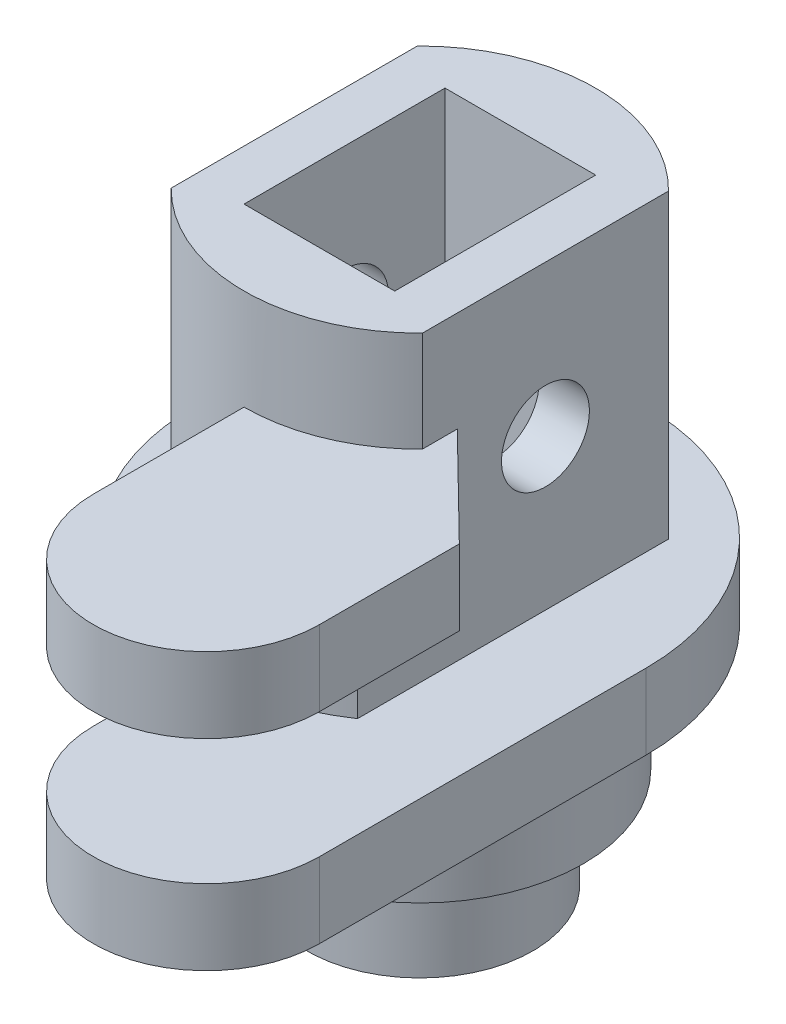
SolidWorks part; units mm, degrees
other "Markup1"
sketch "Sketch25" plane through (9, 15, 17.5) normal (0.6941, 0.3653, 0.6203) x (0.635, -0.7165, -0.2888)
ref_plane "Front Plane" through (0, 0, 0) normal (0, 0, 1) x (1, 0, 0)
ref_plane "Top Plane" through (0, 0, 0) normal (0, 1, 0) x (1, 0, 0)
ref_plane "Right Plane" through (0, 0, 0) normal (1, 0, 0) x (0, 0, -1)
sketch "Sketch1" plane through (0, 0, 0) normal (0, 1, 0) x (1, 0, 0)
  circle A0 centre (0, 0) radius 9
  dimension "D1" = 18
extrude "main body" add sketch "Sketch1" along normal blind 15
sketch "Sketch4" plane through (0, 0, 0) normal (0, -1, 0) x (1, 0, 0)
  circle A0 centre (0, 0) radius 6.5
  circle A1 centre (0, 0) radius 9 construction
  dimension "D1" = 13
extrude "Boss-Extrude3" add sketch "Sketch4" along normal blind 5 contours A0
sketch "Sketch5" plane through (0, -5, 0) normal (0, -1, 0) x (1, 0, 0)
  circle A0 centre (0, 0) radius 4.5
  circle A1 centre (0, 0) radius 6.5 construction
  dimension "D1" = 9
extrude "Boss-Extrude4" add sketch "Sketch5" along normal blind 4 contours A0
ref_plane "Plane1" through (0, 8, 0) normal (0, 1, 0) x (1, 0, 0)
sketch "Sketch9" plane through (0, 0, 0) normal (0, -1, 0) x (1, 0, 0)
  line L0 (0, 9) -> (0, 13)
  line L1 (9, 0) -> (9, 13)
  line L2 (0, 13) -> (9, 13) construction
  circle A0 centre (0, 0) radius 9 construction
  arc A2 (9, 0) -> (0, 9) centre (0, 0) ccw
  arc A3 (9, 13) -> (0, 13) centre (4.5, 13) ccw
  dimension "D2" = 4.5
  dimension "D1" = 4
extrude "arm atttach" add sketch "Sketch9" against normal blind 3
ref_plane "Plane2" through (5, 0, 0) normal (1, 0, 0) x (0, 0, -1)
sketch "Sketch11" plane through (5, 0, 0) normal (1, 0, 0) x (0, 0, -1)
  line L0 (9, 0) -> (9, 15) construction
  line L1 (-9, 15) -> (9, 15)
  line L2 (-9, 15) -> (-9, 3)
  line L3 (-9, 3) -> (9, 3)
  line L4 (9, 15) -> (9, 3)
  dimension "D1" = 12
extrude "Cut-Extrude1" cut sketch "Sketch11" along normal blind 5
sketch "Sketch13" plane through (0, 8, 0) normal (0, 1, 0) x (1, 0, 0)
  line L0 (0, -13) -> (0, -9)
  line L1 (9, -13) -> (9, -7.4292)
  line L2 (9, -7.4292) -> (5, -3.5092)
  line L3 (5, -7.4833) -> (5, 7.4833) construction
  line L4 (5, -3.5092) -> (5, -7.4833)
  arc A0 (0, -13) -> (9, -13) centre (4.5, -13) ccw
  arc A1 (0, -9) -> (5, -7.4833) centre (0, 0) ccw
extrude "arm attach" add sketch "Sketch13" along normal blind 3
ref_plane "Plane4" through (-5, 0, 0) normal (-1, 0, 0) x (0, 0, 1)
sketch "Sketch19" plane through (0, 15, 0) normal (0, 1, 0) x (1, 0, 0)
  line L0 (0, -7) -> (0, -9)
  line L1 (7.0839, -5.5514) -> (5.6441, -4.1405)
  line L2 (9, -7.4292) -> (5, -3.5092) construction
  arc A0 (5.6441, -4.1405) -> (0, -7) centre (0, 0) ccw
  arc A1 (7.0839, -5.5514) -> (0, -9) centre (0, 0) ccw
  dimension "D1" = 14
extrude "Cut-Extrude5" cut sketch "Sketch19" against normal up to surface (12 mm away) up to face at (4.8416, 3, 6.5616)
sketch "Sketch14" plane through (0, 15, 0) normal (0, 1, 0) x (1, 0, 0)
  line L1 (-3, 4) -> (3, 4)
  line L2 (-3, 4) -> (-3, -4)
  line L3 (-3, -4) -> (3, -4)
  line L4 (3, 4) -> (3, -4)
  line L5 (-3, 4) -> (3, -4) construction
  line L6 (-3, -4) -> (3, 4) construction
  point P0 (0, 0)
  dimension "D1" = 6
  dimension "D2" = 8
extrude "blade hole" cut sketch "Sketch14" against normal up to surface (12 mm away) up to face at (1.0369, 3, 5.4786)
sketch "Sketch21" plane through (-5, 0, 0) normal (-1, 0, 0) x (0, 0, 1)
  line L0 (-7, 9) -> (7, 9) construction
  line L1 (-7.5, 15) -> (7.5, 15)
  line L2 (-7.5, 15) -> (-7.5, 3)
  line L3 (-7.5, 3) -> (7.5, 3)
  line L4 (7.5, 15) -> (7.5, 3)
  line L5 (-7.5, 15) -> (7.5, 3) construction
  line L6 (-7.5, 3) -> (7.5, 15) construction
  line L7 (-7, 15) -> (-7, 3) construction
  line L8 (7, 3) -> (7, 15) construction
  point P0 (0, 9)
  dimension "D1" = 12
  dimension "D2" = 15
extrude "face cut" cut sketch "Sketch21" along normal blind 10
sketch "Sketch23" plane through (0, 15, 0) normal (0, 1, 0) x (1, 0, 0)
  circle A0 centre (0, 0) radius 7
  circle A1 centre (0, 0) radius 9
extrude "Cut-Extrude8" cut sketch "Sketch23" against normal up to surface (4 mm away) up to face at (4.6854, 11, 9.7154)
sketch "Sketch24" plane through (-5, 0, 0) normal (-1, 0, 0) x (0, 0, 1)
  line L0 (0, 15) -> (0, 3) construction
  line L1 (4.899, 15) -> (-4.899, 15) construction
  line L2 (9, 3) -> (-9, 3) construction
  circle A0 centre (0, 9) radius 1.75
  dimension "D1" = 3.5
extrude "screw hole" cut sketch "Sketch24" against normal mid plane 30
